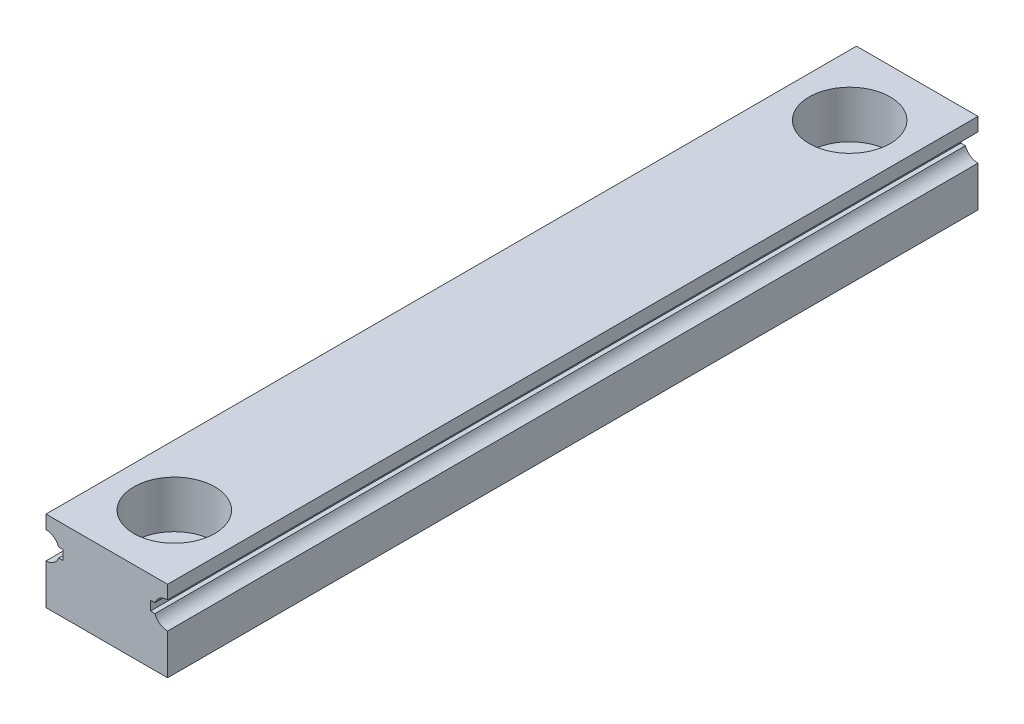
SolidWorks part; units mm, degrees
ref_plane "Front Plane" through (0, 0, 0) normal (0, 0, 1) x (1, 0, 0)
ref_plane "Top Plane" through (0, 0, 0) normal (0, 1, 0) x (1, 0, 0)
ref_plane "Right Plane" through (0, 0, 0) normal (1, 0, 0) x (0, 0, -1)
sketch "Sketch1" plane through (0, 0, 0) normal (0, 0, 1) x (1, 0, 0)
  line L0 (0, 0) -> (0, 5.7299) construction
  line L1 (-4.5, -3) -> (4.5, -3)
  line L2 (-4.5, -3) -> (-4.5, 0)
  line L3 (-4.5, 3) -> (4.5, 3)
  line L4 (4.5, -3) -> (4.5, 0)
  line L5 (-4.5, -3) -> (4.5, 3) construction
  line L6 (-4.5, 3) -> (4.5, -3) construction
  line L7 (-4.5, 2) -> (-4.5, 3)
  line L8 (-3.564, 0.648) -> (-3.2351, 0.648)
  line L9 (3.564, 0.648) -> (3.2351, 0.648)
  line L10 (-3.564, 1.352) -> (-3.2351, 1.352)
  line L11 (-3.2351, 0.648) -> (-3.2351, 1.352)
  line L12 (3.2351, 0.648) -> (3.2351, 1.352)
  line L13 (3.564, 1.352) -> (3.2351, 1.352)
  line L14 (4.5, 2) -> (4.5, 3)
  arc A0 (-3.564, 1.352) -> (-4.5, 2) centre (-4.5, 1) ccw
  arc A1 (-4.5, 0) -> (-3.564, 0.648) centre (-4.5, 1) ccw
  arc A2 (4.5, 0) -> (3.564, 0.648) centre (4.5, 1) cw
  arc A3 (3.564, 1.352) -> (4.5, 2) centre (4.5, 1) cw
  point P0 (0, 0)
  dimension "D3" = 1
  dimension "D1" = 9
  dimension "D2" = 6
  dimension "D4" = 2
extrude "Extrude1" add sketch "Sketch1" along normal blind 60
sketch "Sketch2" plane through (0, 3, 0) normal (0, 1, 0) x (1, 0, 0)
  line L0 (4.5, 0) -> (-4.5, 0) construction
  circle A0 centre (0, -5) radius 1.75
  circle A1 centre (0, -5) radius 3
  dimension "D1" = 3.5
  dimension "D2" = 6
  dimension "D3" = 5
extrude "Extrude2" cut sketch "Sketch2" against normal blind 3.5 contours A1
extrude "Extrude3" cut sketch "Sketch" against normal through all contours A0
sketch "Sketch" plane through (0, 3, 0) normal (0, 1, 0) x (1, 0, 0) same geometry as "Sketch2"
pattern_linear "LPattern1" count 45 spacing 50 along (0, 0, 1) of "Extrude2", "Extrude3"
